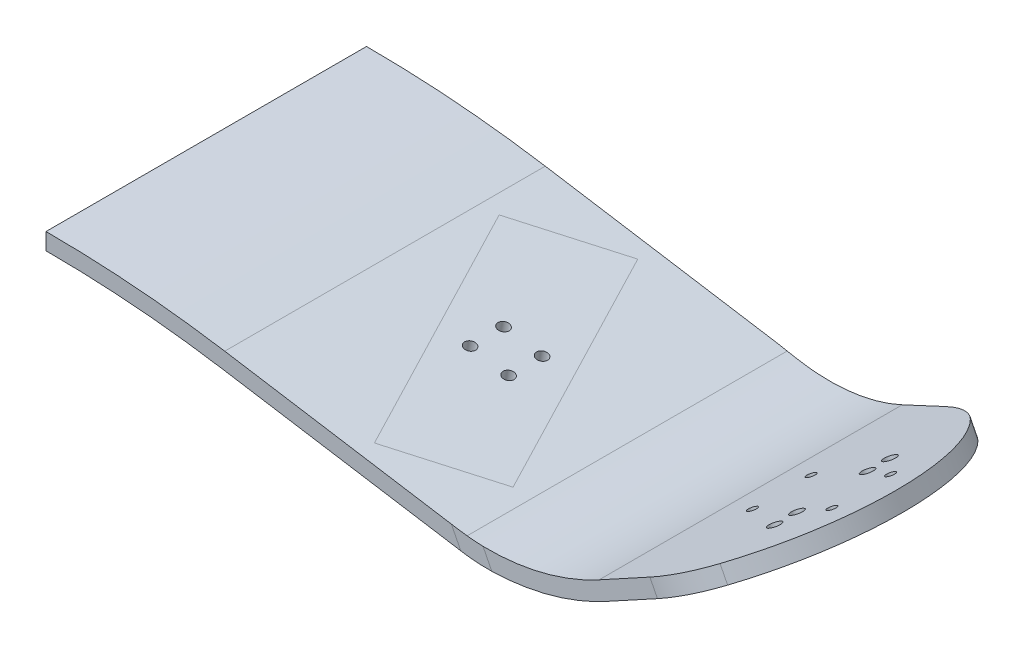
SolidWorks part; units mm, degrees
material "Acrylic (Medium-high impact)"
ref_plane "Front Plane" through (0, 0, 0) normal (0, 0, 1) x (1, 0, 0)
ref_plane "Top Plane" through (0, 0, 0) normal (0, 1, 0) x (1, 0, 0)
ref_plane "Right Plane" through (0, 0, 0) normal (1, 0, 0) x (0, 0, -1)
sketch "Sketch1" plane through (0, 0, 0) normal (0, 0, 1) x (1, 0, 0)
  line L0 (-500, 0) -> (500, 0) construction
  line L1 (0, 0) -> (0, 88.9231) construction
  line L2 (500, 0) -> (500, 70) construction
  line L3 (-500, 0) -> (-500, 70) construction
  line L4 (-500, 70) -> (-396.1345, 17.0779)
  line L5 (500, 70) -> (396.1345, 17.0779)
  line L6 (-300.1386, 1.9849) -> (-126.3682, 29.9107)
  line L7 (300.1386, 1.9849) -> (126.3682, 29.9107)
  arc A0 (-396.1345, 17.0779) -> (-300.1386, 1.9849) centre (-325, 156.6872) ccw
  arc A1 (396.1345, 17.0779) -> (300.1386, 1.9849) centre (325, 156.6872) cw
  arc A2 (-126.3682, 29.9107) -> (126.3682, 29.9107) centre (0, -756.4253) cw
  point P8 (325, 0)
  point P9 (-325, 0)
  dimension "D6" = 40
  dimension "D1" = 1000
  dimension "D2" = 70
  dimension "D3" = 650
  dimension "D4" = 27
  dimension "D5" = 176
extrude "Extrude-Thin1" add sketch "Sketch1" along normal mid plane 230 thin thin type one direction wall 12
sketch "Sketch2" plane through (-69.2902, -135.9897, 0) normal (0.454, 0.891, 0) x (-0.891, 0.454, 0)
  line L0 (477.2826, 0) -> (316.1458, 0) construction
  line L1 (477.2826, 115) -> (477.2826, -115) construction
  line L2 (275.4019, 115) -> (398.4888, 106)
  line L3 (275.4019, -115) -> (398.4888, -106)
  line L9 (360.7116, 115) -> (477.2826, 115) construction
  arc A0 (398.4888, 106) -> (436.8451, 89.8321) centre (393.7487, 41.1731) cw
  arc A1 (398.4888, -106) -> (436.8451, -89.8321) centre (393.7487, -41.1731) ccw
  arc A2 (436.8451, 89.8321) -> (436.8451, -89.8321) centre (357.2826, 0) cw
  dimension "D2" = 120
  dimension "D3" = 9
  dimension "D1" = 65
extrude "Cut-Extrude1" cut sketch "Sketch2" against normal through all and the other way through all flip side to cut
mirror "Mirror1" about plane through (0, 0, 0) normal (1, 0, 0) of "Cut-Extrude1"
fillet "Fillet1" radius 250 4 edges at (-305.3489, 7.3439, -115) (305.3489, 7.3439, -115) (305.3489, 7.3439, 115) (-305.3489, 7.3439, 115)
chamfer "Chamfer1" [suppressed] distance 3 angle 45
sketch "Sketch3" plane through (-9.7713, 60.8024, 0) normal (-0.1587, 0.9873, 0) x (-0.9873, -0.1587, 0)
  line L0 (120.0214, 0) -> (296.0214, 0) construction
  line L3 (120.0214, 115) -> (120.0214, -115) construction
  line L4 (296.0214, 114.8333) -> (296.0214, -114.8333) construction
  line L5 (208.0214, 0) -> (208.0214, 77.1372) construction
  circle A0 centre (222.0214, 12) radius 4
  circle A1 centre (222.0214, -12) radius 4
  circle A2 centre (194.0214, -12) radius 4
  circle A3 centre (194.0214, 12) radius 4
  dimension "D1" = 28
  dimension "D2" = 24
  dimension "D3" = 8
extrude "Binding Holes" cut sketch "Sketch3" against normal through all
sketch "Sketch4" plane through (430.771, -6.8544, -35.3505) normal (0.1587, 0.9873, 0) x (-0.9873, 0.1587, 0)
  line L0 (130.3801, 35.3505) -> (306.3801, 35.3505) construction
  line L1 (130.3801, 150.1838) -> (130.3801, -79.4828) construction
  line L2 (306.3801, 150.3505) -> (306.3801, -79.6495) construction
  line L5 (218.3801, 35.3505) -> (218.3801, 92.6366) construction
  circle A0 centre (232.3801, 47.3505) radius 4
  circle A1 centre (232.3801, 23.3505) radius 4
  circle A2 centre (204.3801, 23.3505) radius 4
  circle A3 centre (204.3801, 47.3505) radius 4
  dimension "D1" = 28
  dimension "D2" = 24
  dimension "D3" = 8
extrude "Cut-Extrude2" cut sketch "Sketch4" against normal through all
hole_wizard "M6 Clearance Hole1" positions "Sketch6" profile "Sketch5" hole size "M6" standard "Ansi Metric" end condition through all
sketch "Sketch6" plane through (-49.3311, -146.1594, -63.3454) normal (0.454, 0.891, 0) x (-0.891, 0.454, 0)
  line L0 (383.1122, 63.3454) -> (457.5491, 63.3454) construction
  line L2 (383.1122, 172.1076) -> (383.1122, -45.4168) construction
  point P0 (472.1122, 84.3454)
  point P1 (408.1122, 84.3454)
  point P13 (408.1122, 42.3454)
  point P14 (472.1122, 42.3454)
  dimension "D1" = 64
  dimension "D2" = 42
  dimension "D3" = 25
sketch "Sketch5" plane through (-469.9862, 68.1751, 21) normal (0, 0, 1) x (-0.891, 0.454, 0)
  line L0 (0, 0) -> (0, 74.3705)
  line L1 (0, 74.3705) -> (3.3, 74.3705)
  line L2 (3.3, 74.3705) -> (3.3, 0)
  line L5 (3.3, 0) -> (0, 0)
  line L11 (0, -6.35) -> (0, 107.95) construction
  dimension "Thru Hole Dia." = 6.6
  dimension "Thru Hole Depth" = 74.3705
hole_wizard "M8 Clearance Hole1" positions "Sketch8" profile "Sketch7" hole size "M8" standard "Ansi Metric" end condition through all
sketch "Sketch8" plane through (-70.6163, -135.314, -54.2109) normal (0.454, 0.891, 0) x (-0.891, 0.454, 0)
  line L0 (359.2233, 54.2109) -> (455.7072, 54.2109) construction
  line L2 (359.2233, 162.9732) -> (359.2233, -54.5513) construction
  circle A3 centre (384.2233, 75.2109) radius 3.3 construction
  point P1 (424.9363, 95.5609)
  point P3 (424.9363, 79.5609)
  point P13 (424.9363, 12.8609)
  point P14 (424.9363, 28.8609)
  dimension "D1" = 16
  dimension "D2" = 50.7
  dimension "D3" = 40.713
sketch "Sketch7" plane through (-449.2373, 57.603, 41.35) normal (0, 0, 1) x (-0.891, 0.454, 0)
  line L0 (0, 0) -> (0, 74.3705)
  line L1 (0, 74.3705) -> (4.5, 74.3705)
  line L2 (4.5, 74.3705) -> (4.5, 0)
  line L5 (4.5, 0) -> (0, 0)
  line L11 (0, -6.35) -> (0, 107.95) construction
  dimension "Thru Hole Dia." = 9
  dimension "Thru Hole Depth" = 74.3705
mirror "Mirror2" about plane through (0, 0, 0) normal (1, 0, 0) of "M6 Clearance Hole1", "M8 Clearance Hole1"
sketch "Sketch9" plane through (0, 0, 0) normal (0, 1, 0) x (1, 0, 0)
  line L0 (128.2722, 115) -> (-128.2722, 115) construction
  line L1 (0, -115) -> (-500, -115)
  line L2 (0, -115) -> (0, 115)
  line L3 (0, 115) -> (-500, 115)
  line L4 (-500, -115) -> (-500, 115)
  line L5 (-128.2722, -115) -> (128.2722, -115) construction
  ellipse E0 centre (-393.0792, 0) end of major axis (-393.0792, -120) minor radius 106.9208 (-463.9699, 89.8321) -> (-463.9699, -89.8321) ccw construction
extrude "Cut-Extrude3" cut sketch "Sketch9" along normal through all
sketch "Sketch10" plane through (9.7713, 60.8024, 0) normal (0.1587, 0.9873, 0) x (-0.9873, 0.1587, 0)
  line L0 (-216.6458, 103) -> (-132.0214, -70.0527)
  line L1 (-216.6458, 103) -> (-284.0214, 70.0527)
  line L2 (-132.0214, -70.0527) -> (-199.397, -103)
  line L3 (-284.0214, 70.0527) -> (-199.397, -103)
  line L4 (-296.0214, 114.8333) -> (-296.0214, -114.8333) construction
  line L5 (-284.7203, 115) -> (-120.0214, 115) construction
  line L6 (-120.0214, 115) -> (-120.0214, -115) construction
  line L7 (-284.7203, -115) -> (-120.0214, -115) construction
  dimension "D1" = 75
  dimension "D2" = 12
  dimension "D3" = 12
  dimension "D4" = 12
  dimension "D5" = 12
split line "Split Line1"
sketch "Sketch11" plane through (74.7381, -146.6818, 0) normal (0.454, -0.891, 0) x (0.891, 0.454, 0)
  line L0 (360.7116, 108.7622) -> (360.7116, -108.7622) construction
  circle A0 centre (410.7116, 0) radius 37.5
  dimension "D1" = 75
  dimension "D2" = 50
split line "Split Line2"
